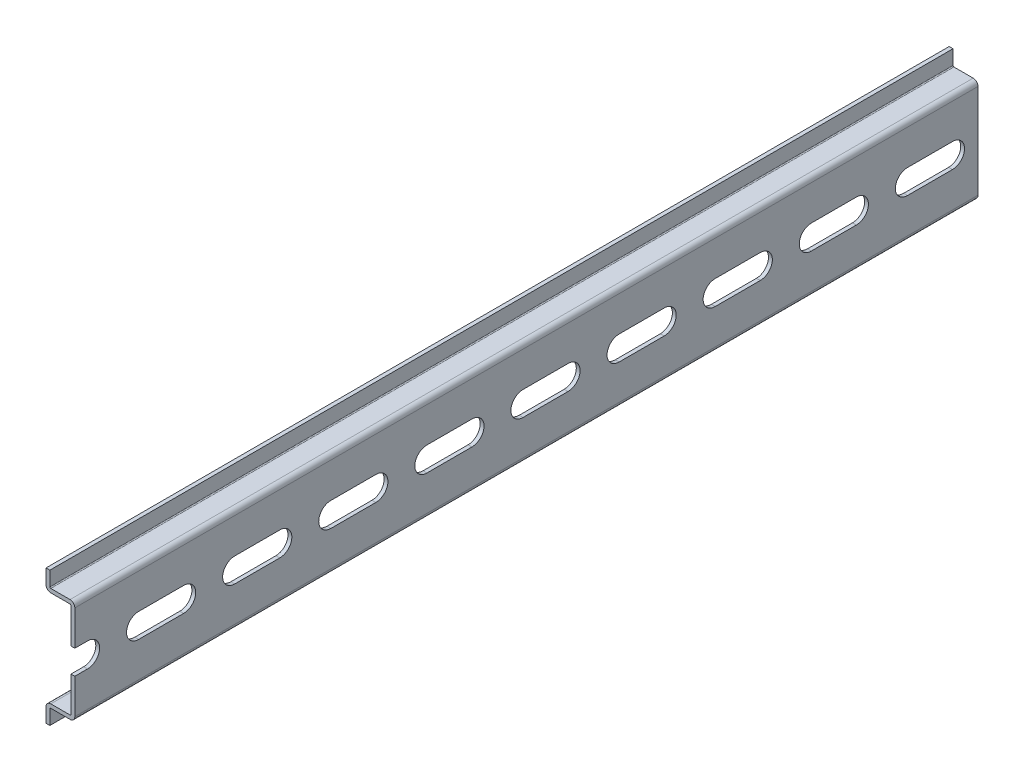
SolidWorks part; units mm, degrees
ref_plane "Front Plane" through (0, 0, 0) normal (0, 0, 1) x (1, 0, 0)
ref_plane "Top Plane" through (0, 0, 0) normal (0, 1, 0) x (1, 0, 0)
ref_plane "Right Plane" through (0, 0, 0) normal (1, 0, 0) x (0, 0, -1)
sketch "Sketch1" plane through (0, 0, 0) normal (0, 0, 1) x (1, 0, 0)
  line L0 (0, -13.5) -> (0, 13.5) construction
  line L1 (0, 13.5) -> (-6.5, 13.5) construction
  line L2 (-6.5, 13.5) -> (-6.5, 17.5) construction
  line L3 (0, -13.5) -> (-6.5, -13.5) construction
  line L4 (-6.5, -13.5) -> (-6.5, -17.5) construction
  line L5 (-7.5, 0) -> (0, 0) construction
  line L6 (-6.5, 17.5) -> (-7.5, 17.5) construction
  line L7 (-7.5, 0) -> (-7.5, 17.5) construction
  dimension "D1" = 27
  dimension "Height" = 35
  dimension "Depth" = 7.5
  dimension "Metal Thickness" = 1
sketch "Sketch2" plane through (0, 0, 0) normal (1, 0, 0) x (0, 0, -1)
  line L0 (0, 0) -> (-234.95, 0) construction
  line L1 (-62.5, 17.5) -> (-62.5, -17.5) construction
  line L2 (-172.45, 17.5) -> (-172.45, -17.5) construction
  line L3 (-62.5, 17.5) -> (-172.45, 17.5) construction
  line L4 (-117.475, 0) -> (-117.475, 17.5) construction
  point P8 (-172.45, 0)
  point P9 (-62.5, 0)
  point P14 (-117.475, 17.5)
  dimension "Length" = 234.95
  dimension "D1" = 62.5
sketch "Sketch3" plane through (0, 0, 0) normal (0, 0, 1) x (1, 0, 0)
  line L0 (-6.5, -13.5) -> (-6.5, -17.5) construction
  line L1 (0, -13.5) -> (-6.5, -13.5) construction
  line L2 (0, -13.5) -> (0, 13.5) construction
  line L3 (0, 13.5) -> (-6.5, 13.5) construction
  line L4 (-6.5, 13.5) -> (-6.5, 17.5) construction
  line L5 (-6.5, -13.5) -> (-6.5, -17.5)
  line L6 (0, -13.5) -> (-6.5, -13.5)
  line L7 (0, -13.5) -> (0, 13.5)
  line L8 (0, 13.5) -> (-6.5, 13.5)
  line L9 (-6.5, 13.5) -> (-6.5, 17.5)
extrude "Extrude-Thin1" add sketch "Sketch3" along normal up to vertex (234.95 mm away) thin up to point (0, 0, 234.95) thin type one direction reverse wall 1
sketch "Sketch4" plane through (0, 0, 0) normal (1, 0, 0) x (0, 0, -1)
  line L0 (0, 0) -> (-62.1077, 0) construction
  line L1 (-6.65, 0) -> (-18.35, 0) construction
  line L2 (-6.65, -3.15) -> (-18.35, -3.15)
  line L3 (-6.65, 3.15) -> (-18.35, 3.15)
  arc A0 (-6.65, -3.15) -> (-6.65, 3.15) centre (-6.65, 0) ccw
  arc A1 (-18.35, 3.15) -> (-18.35, -3.15) centre (-18.35, 0) ccw
  point P5 (-12.5, 0)
  point P10 (-3.5, 0)
  point P11 (-21.5, 0)
  point P12 (-37.5, 0)
  dimension "D1" = 18
  dimension "Mounting Hole Diameter" = 6.3
  dimension "D3" = 12.5
  dimension "Mounting Hole C to C" = 25
extrude "Cut-Extrude1" cut sketch "Sketch4" against normal through all both and the other way through all
pattern_linear "LPattern1" count 37 spacing 25 along (0, 0, 1) of "Cut-Extrude1"
fillet "Fillet1" radius 0.25 4 edges at (-6.5, 13.5, 117.475) (-6.5, -13.5, 117.475) (-1, 12.5, 117.475) (-1, -12.5, 117.475)
fillet "Fillet2" radius 1.25 4 edges at (-7.5, -12.5, 117.475) (0, -13.5, 117.475) (0, 13.5, 117.475) (-7.5, 12.5, 117.475)
ref_plane "Contact Plane 1" through (-1, 0, 0) normal (-1, 0, 0) x (0, 0, 1)
equation "\"D3@LPattern1\" = \"Mounting Hole C to C@Sketch4\""
equation "\"D5@Extrude-Thin1\"=\"Metal Thickness@Sketch1\""
equation "\"D3@Sketch4\"=\"Mounting Hole C to C@Sketch4\"/2"
equation "\"D1@LPattern1\"=\"Length@Sketch2\"/\"Mounting Hole Diameter@Sketch4\""
